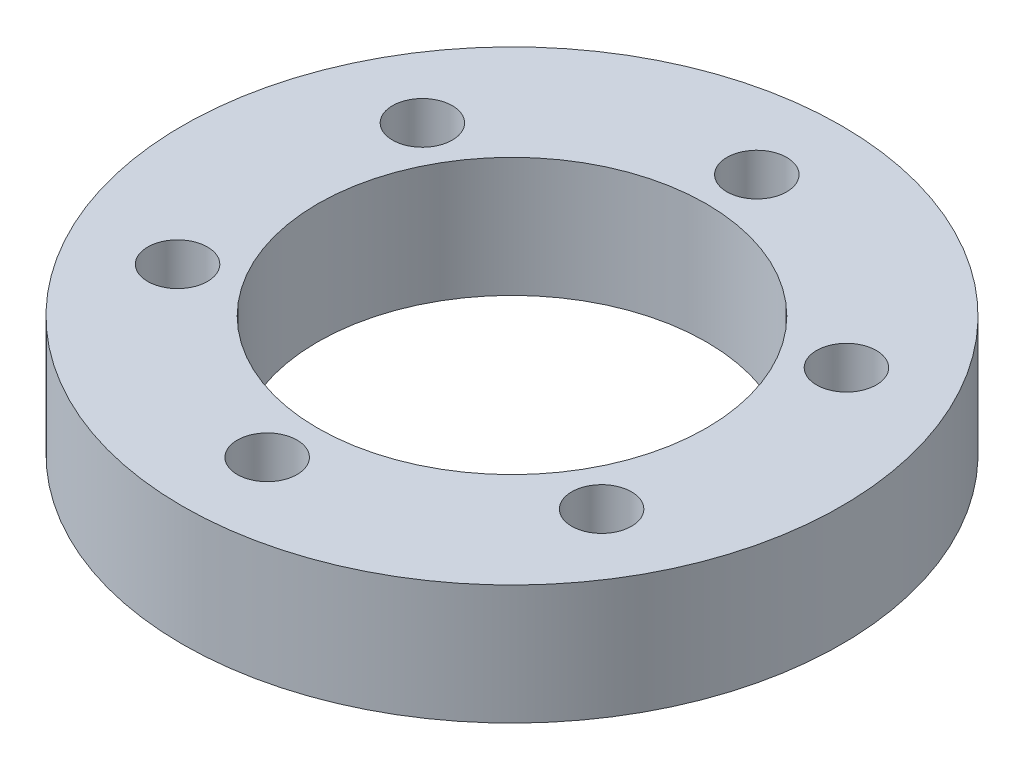
SolidWorks part; units mm, degrees
material "6061-T6 (SS)"
ref_plane "Front Plane" through (0, 0, 0) normal (0, 0, 1) x (1, 0, 0)
ref_plane "Top Plane" through (0, 0, 0) normal (0, 1, 0) x (1, 0, 0)
ref_plane "Right Plane" through (0, 0, 0) normal (1, 0, 0) x (0, 0, -1)
sketch "Sketch1" plane through (0, 0, 0) normal (0, 1, 0) x (1, 0, 0)
  circle A0 centre (0, 0) radius 35
  circle A1 centre (0, 0) radius 10
  dimension "D1" = 70
  dimension "D2" = 20
extrude "Boss-Extrude1" add sketch "Sketch1" against normal blind 12.7
sketch "Sketch3" plane through (0, -12.7, 0) normal (0, -1, 0) x (1, 0, 0)
  circle A0 centre (0, 0) radius 20.6375
  dimension "D1" = 41.275
extrude "Cut-Extrude1" cut sketch "Sketch3" against normal blind 12.7
sketch "Sketch4" plane through (0, -12.7, 0) normal (0, -1, 0) x (1, 0, 0)
  circle A0 centre (0, 26) radius 3.175
  dimension "D2" = 6.35
  dimension "D1" = 26
extrude "Cut-Extrude2" cut sketch "Sketch4" against normal through all
pattern_circular "CirPattern1" count 6 over 360 about axis through (0, -12.7, 0) along (0, -1, 0) of "Cut-Extrude2"
equation "\"D2@Sketch4\"=0.25in"
equation "\"D1@Sketch3\"=1in + 5in/8"
equation "\"D1@Cut-Extrude1\"=0.5in"
